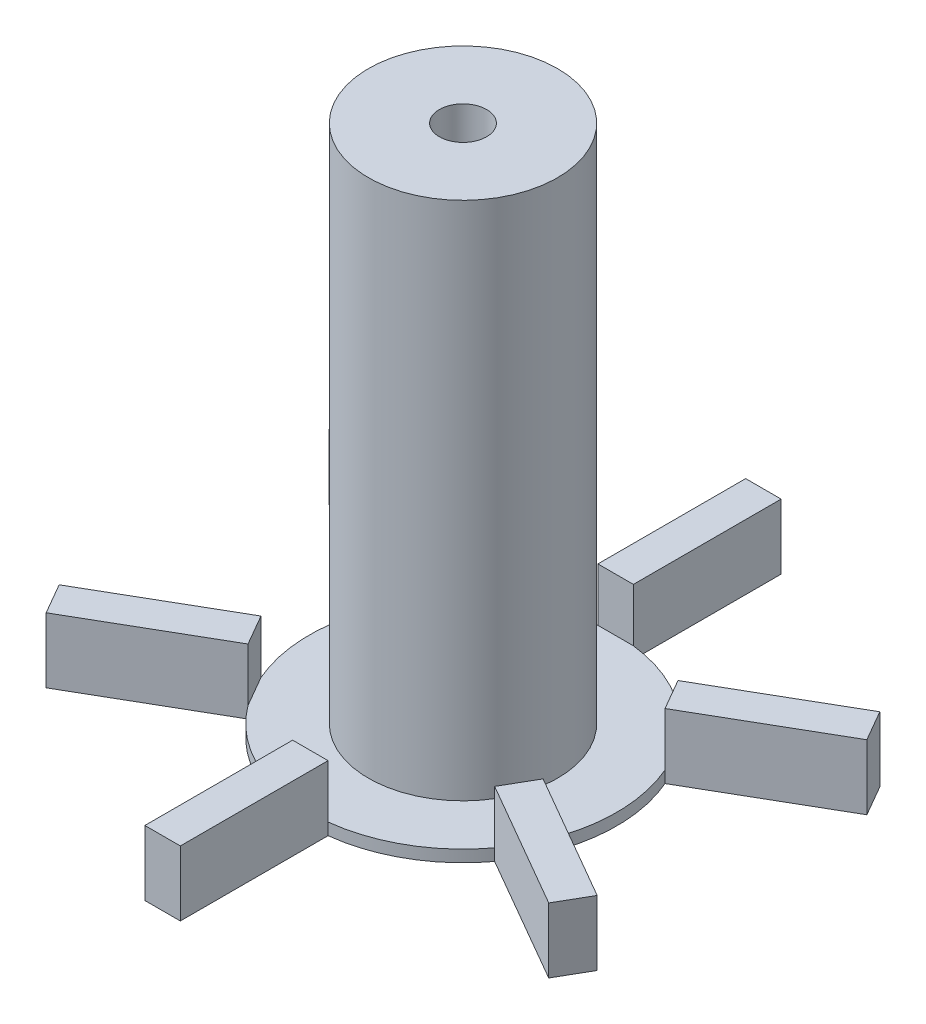
SolidWorks part; units mm, degrees
ref_plane "Front Plane" through (0, 0, 0) normal (0, 0, 1) x (1, 0, 0)
ref_plane "Top Plane" through (0, 0, 0) normal (0, 1, 0) x (1, 0, 0)
ref_plane "Right Plane" through (0, 0, 0) normal (1, 0, 0) x (0, 0, -1)
sketch "Sketch1" plane through (0, 0, 0) normal (0, 1, 0) x (1, 0, 0)
  line L48 (-1.5, -12.9132) -> (1.5, -12.9132)
  line L55 (1.5, -12.9132) -> (1.5, -25.4132)
  line L62 (1.5, -25.4132) -> (-1.5, -25.4132)
  line L69 (-1.5, -25.4132) -> (-1.5, -12.9132)
  line L70 (-22.7585, -11.4075) -> (-11.9331, -5.1575)
  line L71 (-11.9331, -5.1575) -> (-10.4331, -7.7556)
  line L72 (-10.4331, -7.7556) -> (-21.2585, -14.0056)
  line L73 (-21.2585, -14.0056) -> (-22.7585, -11.4075)
  line L74 (-21.2585, 14.0056) -> (-10.4331, 7.7556)
  line L75 (-10.4331, 7.7556) -> (-11.9331, 5.1575)
  line L76 (-11.9331, 5.1575) -> (-22.7585, 11.4075)
  line L77 (-22.7585, 11.4075) -> (-21.2585, 14.0056)
  line L78 (1.5, 25.4132) -> (1.5, 12.9132)
  line L79 (1.5, 12.9132) -> (-1.5, 12.9132)
  line L80 (-1.5, 12.9132) -> (-1.5, 25.4132)
  line L81 (-1.5, 25.4132) -> (1.5, 25.4132)
  line L82 (22.7585, 11.4075) -> (11.9331, 5.1575)
  line L83 (11.9331, 5.1575) -> (10.4331, 7.7556)
  line L84 (10.4331, 7.7556) -> (21.2585, 14.0056)
  line L85 (21.2585, 14.0056) -> (22.7585, 11.4075)
  line L86 (21.2585, -14.0056) -> (10.4331, -7.7556)
  line L87 (10.4331, -7.7556) -> (11.9331, -5.1575)
  line L88 (11.9331, -5.1575) -> (22.7585, -11.4075)
  line L89 (22.7585, -11.4075) -> (21.2585, -14.0056)
  circle A1 centre (0, 0) radius 2
  circle A2 centre (0, 0) radius 8
  arc A3 (1.5, -12.9132) -> (10.4331, -7.7556) centre (0, 0) ccw
  arc A4 (-10.4331, -7.7556) -> (-1.5, -12.9132) centre (0, 0) ccw
  arc A5 (-11.9331, 5.1575) -> (-11.9331, -5.1575) centre (0, 0) ccw
  arc A6 (-1.5, 12.9132) -> (-10.4331, 7.7556) centre (0, 0) ccw
  arc A7 (10.4331, 7.7556) -> (1.5, 12.9132) centre (0, 0) ccw
  arc A8 (11.9331, -5.1575) -> (11.9331, 5.1575) centre (0, 0) ccw
  point P9 (0, -12.9132)
  point P31 (0, 0)
  point P32 (0, 0)
  point P33 (0, 0)
  point P46 (0.0289, 0.0554)
  dimension "D1" = 4
  dimension "D2" = 16
  dimension "D3" = 5
  dimension "D4" = 3
  dimension "D5" = 12.5
  dimension "D6" = 6
extrude "Boss-Extrude1" add sketch "Sketch1" along normal blind 45 contours A1 region at (-7.7737, 0, 0)
extrude "Boss-Extrude2" add sketch "Sketch1<3>" along normal blind 5.5 contours L62 | L69 L48 L55 L62 | L70 L71 L72 L73 | L74 L75 L76 L77 | L78 L79 L80 L81 | L82 L83 L84 L85 | L86 L87 L88 L89
sketch "Sketch1<3>" plane through (0, 0, 0) normal (0, 1, 0) x (1, 0, 0) same geometry as "Sketch1"
extrude "Boss-Extrude3" add sketch "Sketch1<4>" along normal blind 1 contours L87 A8 L83 A7 L79 A6 L75 A5 L71 A4 L48 A3 A2 region at (-6.3168, 0, 10.941)
sketch "Sketch1<4>" plane through (0, 0, 0) normal (0, 1, 0) x (1, 0, 0) same geometry as "Sketch1"
